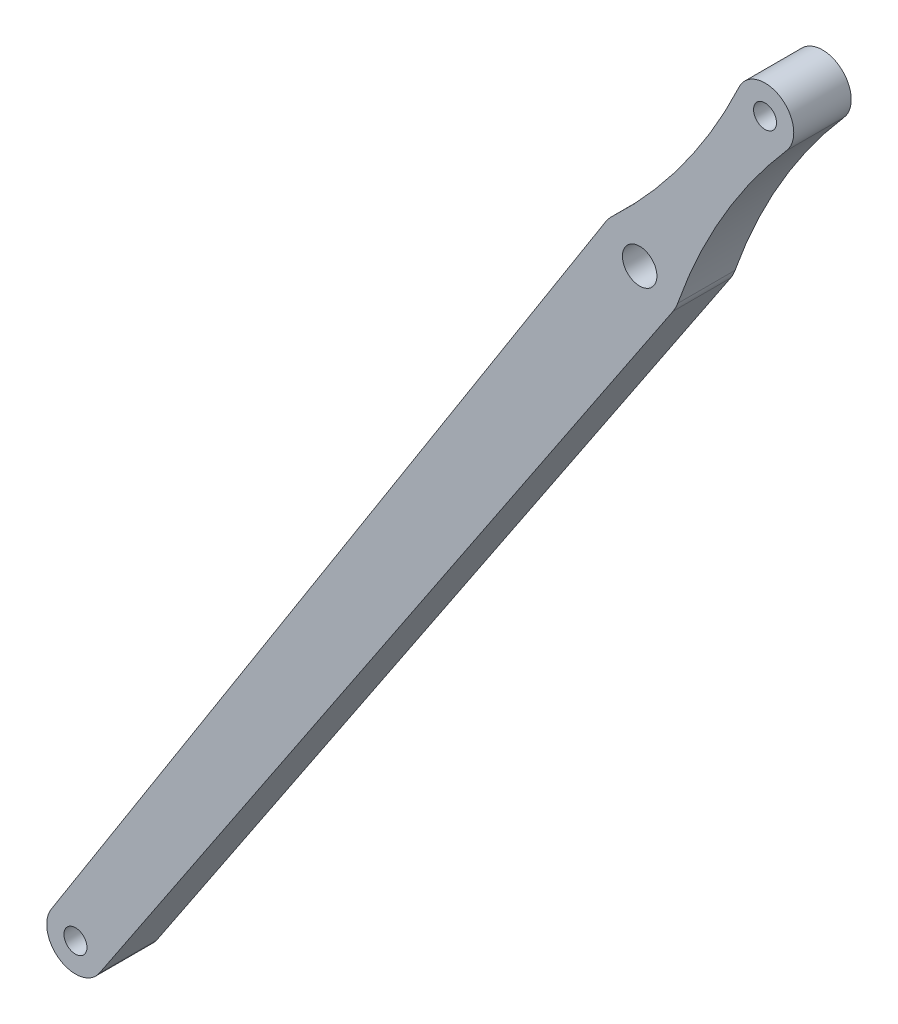
SolidWorks part; units mm, degrees
ref_plane "Front Plane" through (0, 0, 0) normal (0, 0, 1) x (1, 0, 0)
ref_plane "Top Plane" through (0, 0, 0) normal (0, 1, 0) x (1, 0, 0)
ref_plane "Right Plane" through (0, 0, 0) normal (1, 0, 0) x (0, 0, -1)
sketch "Sketch1" plane through (0, 0, 0) normal (0, 0, 1) x (1, 0, 0)
  line L0 (-151.6608, 111.4603) -> (-248.1912, -40.4538)
  line L3 (-139.9294, 103.8215) -> (-239.8117, -45.91)
  circle A2 centre (-145.7527, 107.7061) radius 7
  circle A3 centre (-243.9711, -43.1353) radius 5
  circle A4 centre (-123.9264, 141.2264) radius 5
  arc A5 (-150.5493, 112.8044) -> (-128.4571, 143.3412) centre (-219.0718, 185.6375) ccw
  arc A6 (-120.1595, 137.9384) -> (-139.1498, 105.3818) centre (-44.8233, 72.1778) ccw
  circle A7 centre (-243.9711, -43.1353) radius 2 construction
  circle A8 centre (-243.9711, -43.1353) radius 2
  circle A9 centre (-145.7527, 107.7061) radius 3 construction
  circle A10 centre (-145.7527, 107.7061) radius 3
  circle A11 centre (-123.9264, 141.2264) radius 2 construction
  circle A12 centre (-123.9264, 141.2264) radius 2
  dimension "D1" = 14
  dimension "D2" = 10
  dimension "D3" = 10
  dimension "D4" = 100
  dimension "D5" = 100
extrude "Boss-Extrude1" add sketch "Sketch1" along normal blind 5 and the other way blind 5 contours A3 L3 A2 L0 | A3 | A2 | A6 A4 A5 A2 | A4 region at (-192.8455, 35.3822, 0) region at (-150.9945, 112.0409, 0) region at (-242.6143, -38.4701, 0) region at (-134.7578, 124.5918, 0) region at (-122.8739, 145.9696, 0)
